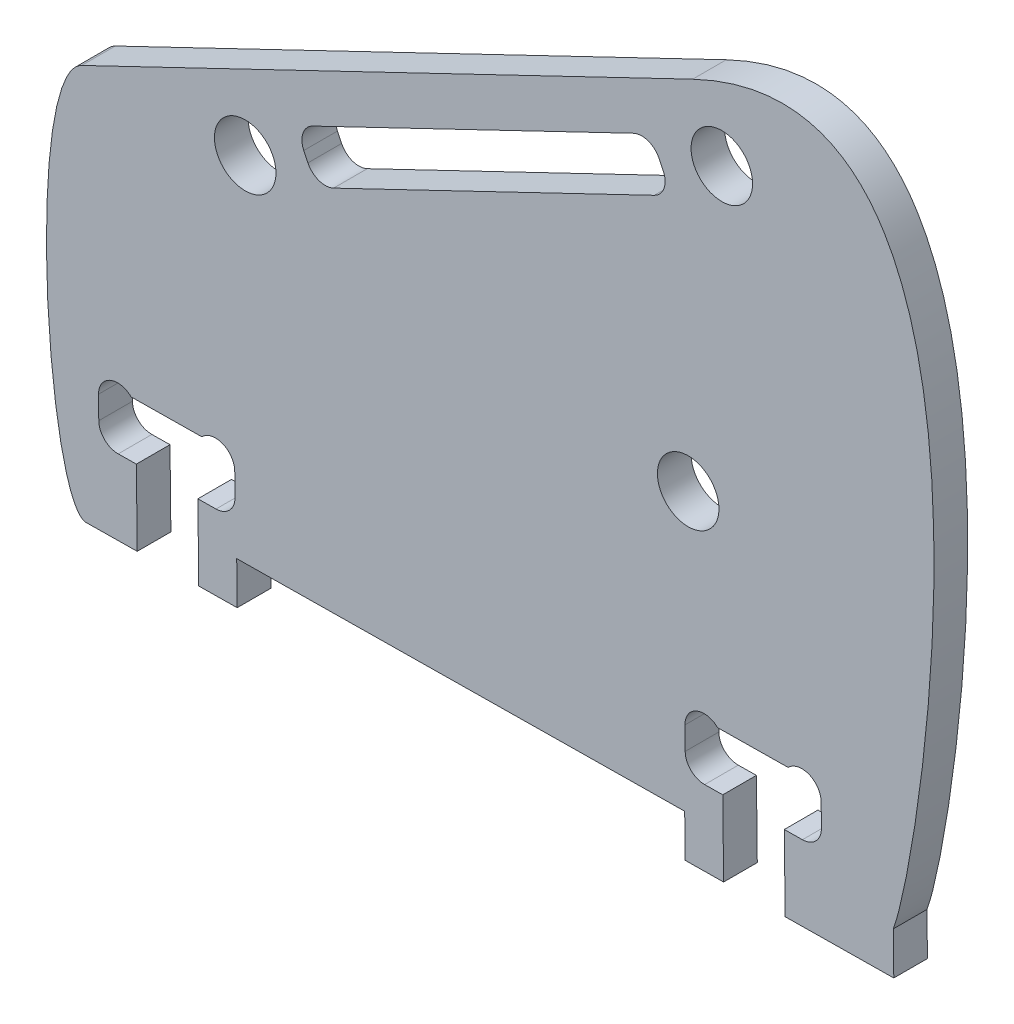
SolidWorks part; units mm, degrees
ref_plane "Front Plane" through (0, 0, 0) normal (0, 0, 1) x (1, 0, 0)
ref_plane "Top Plane" through (0, 0, 0) normal (0, 1, 0) x (1, 0, 0)
ref_plane "Right Plane" through (0, 0, 0) normal (1, 0, 0) x (0, 0, -1)
sketch "Sketch2" plane through (277.9441, -368.7823, 0) normal (0, 0, 1) x (0.9999, 0.0116, 0)
  line L0 (-273.6458, 371.9829) -> (-231.6458, 371.9829)
  line L1 (-237.0451, 403.462) -> (-231.9737, 392.5863)
  line L2 (-273.6458, 390.2567) -> (-231.6458, 390.2567) construction
  line L3 (-269.3958, 375.2829) -> (-238.8958, 375.2829) construction
  line L4 (-238.8958, 373.9829) -> (-238.8958, 371.9829) construction
  line L5 (-241.6964, 405.155) -> (-273.6458, 390.2567)
  line L6 (-273.6458, 390.2567) -> (-273.6458, 371.9829)
  line L7 (-242.1458, 376.5829) -> (-235.6458, 376.5829)
  line L8 (-265.1407, 390.3609) -> (-240.2172, 401.9829) construction
  line L9 (-260.534, 391.1298) -> (-243.7673, 398.9482)
  line L10 (-261.8629, 391.6135) -> (-262.0742, 392.0666)
  line L11 (-243.2836, 400.2771) -> (-243.4949, 400.7303)
  line L12 (-261.5905, 393.3955) -> (-244.8238, 401.214)
  line L13 (-261.4403, 390.7072) -> (-243.9175, 401.6366) construction
  line L14 (-270.1458, 388.0269) -> (-240.2172, 401.9829) construction
  line L15 (-242.861, 399.3708) -> (-262.4968, 392.9729) construction
  line L16 (-254.1458, 375.2829) -> (-254.1458, 371.9829) construction
  line L17 (-242.1458, 376.5829) -> (-242.1458, 373.9829)
  line L18 (-242.1458, 373.9829) -> (-235.6458, 373.9829)
  line L19 (-235.6458, 376.5829) -> (-235.6458, 373.9829)
  line L20 (-242.1458, 376.5829) -> (-235.6458, 373.9829) construction
  line L21 (-242.1458, 373.9829) -> (-235.6458, 376.5829) construction
  line L22 (-242.1458, 376.5829) -> (-239.5458, 373.9829) construction
  line L23 (-240.4958, 371.9829) -> (-237.2958, 371.9829)
  line L24 (-240.4958, 371.9829) -> (-240.4958, 373.9829)
  line L25 (-240.4958, 373.9829) -> (-237.2958, 373.9829)
  line L26 (-237.2958, 371.9829) -> (-237.2958, 373.9829)
  line L27 (-240.4958, 371.9829) -> (-237.2958, 373.9829) construction
  line L28 (-240.4958, 373.9829) -> (-237.2958, 371.9829) construction
  line L29 (-238.8958, 376.5829) -> (-238.8958, 373.9829) construction
  line L30 (-242.4387, 374.69) -> (-242.4387, 375.8758)
  line L31 (-235.3529, 375.8758) -> (-235.3529, 374.69)
  line L32 (-267.7958, 371.9829) -> (-267.7958, 373.9829)
  line L33 (-270.9958, 371.9829) -> (-270.9958, 373.9829)
  line L34 (-266.1458, 373.9829) -> (-272.6458, 373.9829)
  line L35 (-272.9387, 375.8758) -> (-272.9387, 374.69)
  line L36 (-266.1458, 376.5829) -> (-272.6458, 376.5829)
  line L37 (-265.8529, 374.69) -> (-265.8529, 375.8758)
  line L38 (-241.4387, 373.69) -> (-236.3529, 373.69)
  line L39 (-231.6458, 391.1072) -> (-231.6458, 371.9829)
  line L40 (-266.8529, 373.69) -> (-271.9387, 373.69)
  line L42 (-270.9958, 371.9829) -> (-273.6458, 371.9829)
  line L43 (-270.9958, 371.9829) -> (-270.9958, 369.7829)
  line L44 (-270.9958, 369.7829) -> (-273.6458, 369.7829)
  line L45 (-273.6458, 371.9829) -> (-273.6458, 369.7829)
  line L46 (-231.6458, 371.9829) -> (-237.2958, 371.9829)
  line L47 (-231.6458, 371.9829) -> (-231.6458, 369.7829)
  line L48 (-231.6458, 369.7829) -> (-237.2958, 369.7829)
  line L49 (-237.2958, 371.9829) -> (-237.2958, 369.7829)
  line L50 (-267.7958, 371.9829) -> (-265.7958, 371.9829)
  line L51 (-267.7958, 371.9829) -> (-267.7958, 369.7829)
  line L52 (-267.7958, 369.7829) -> (-265.7958, 369.7829)
  line L53 (-265.7958, 371.9829) -> (-265.7958, 369.7829)
  line L54 (-240.4958, 371.9829) -> (-242.4958, 371.9829)
  line L55 (-240.4958, 371.9829) -> (-240.4958, 369.7829)
  line L56 (-240.4958, 369.7829) -> (-242.4958, 369.7829)
  line L57 (-242.4958, 371.9829) -> (-242.4958, 369.7829)
  circle A0 centre (-242.1458, 386.4829) radius 1.6
  circle A1 centre (-265.1407, 390.3609) radius 1.6
  circle A2 centre (-240.2172, 401.9829) radius 1.6
  circle A3 centre (-270.1458, 388.0269) radius 3.5
  circle A4 centre (-240.2172, 401.9829) radius 3.5
  arc A5 (-262.0742, 392.0666) -> (-261.5905, 393.3955) centre (-261.1679, 392.4892) cw
  circle A6 centre (-235.1458, 391.1072) radius 3.5
  circle A7 centre (-241.4387, 375.8758) radius 1
  circle A8 centre (-236.3529, 375.8758) radius 1
  circle A9 centre (-236.3529, 374.69) radius 1
  circle A10 centre (-241.4387, 374.69) radius 1
  arc A11 (-261.8629, 391.6135) -> (-260.534, 391.1298) centre (-260.9566, 392.0361) ccw
  arc A12 (-243.7673, 398.9482) -> (-243.2836, 400.2771) centre (-244.1899, 399.8545) ccw
  circle A13 centre (-271.9387, 374.69) radius 1
  circle A14 centre (-271.9387, 375.8758) radius 1
  circle A15 centre (-266.8529, 375.8758) radius 1
  circle A16 centre (-266.8529, 374.69) radius 1
  arc A17 (-243.4949, 400.7303) -> (-244.8238, 401.214) centre (-244.4012, 400.3077) ccw
  spline S0 degree 3 poles (-273.6458, 369.7829) (-275.7044, 369.8278) (-276.7083, 388.8286) (-273.6458, 390.2567) knots 0 0 0 0 1 1 1 1
  spline S1 degree 3 poles (-241.6964, 405.155) (-223.9419, 413.434) (-230.011, 376.1612) (-231.6458, 371.9829) knots 0 0 0 0 1 1 1 1
  point P10 (-252.6789, 396.1719)
  point P15 (-240.2172, 401.9829)
  point P21 (-238.8958, 372.9829)
  dimension "D1" = 3.2
  dimension "D10" = 3.2
  dimension "D13" = 20.5
  dimension "D2" = 7
  dimension "D17" = 1
  dimension "D11" = 45
  dimension "D14" = 2
  dimension "D3" = 30
  dimension "D4" = 12
  dimension "D5" = 30.5
  dimension "D6" = 4.25
  dimension "D7" = 6.5
  dimension "D8" = 2.6
  dimension "D9" = 2
  dimension "D12" = 2.5
  dimension "D15" = 25
  dimension "D16" = 14.5
  dimension "D18" = 12
  dimension "D19" = 42
  dimension "D20" = 2.2
  dimension "D21" = 2
extrude "Base shape" add sketch "Sketch2" along normal blind 1.75 contours A17 L11 A4 L5 A3 L6 L0 L39 A6 L1 A12 L9 A11 L10 A5 L12 A1 A0 | A3 | A6 | A4 A2 | S0 L45 L6 | A3 L5 L6 | S1 A4 L1 A6 L39 | L0 L45 L44 L43 | L53 L0 L51 L52 | L0 L57 L56 L55 | L0 L49 L48 L47 region at (22.3547, 12.8494, 0) region at (-0.9176, 8.1883, 0) region at (1.3377, -1.0845, 0) region at (40.9915, 23.0224, 0) region at (0.2187, 18.0051, 0) region at (3.3136, 16.0836, 0) region at (6.8623, -1.0204, 0) region at (34.2042, 33.5951, 0) region at (32.1606, -0.7268, 0) region at (39.1851, -0.6453, 0) region at (38.2755, 19.5698, 0)
sketch "Sketch3" plane through (0, 0, 1.75) normal (0, 0, 1) x (1, 0, 0)
  circle A0 centre (8.2913, 18.4755) radius 3
  circle A1 centre (31.3296, 14.8646) radius 3
  circle A2 centre (33.0782, 30.3859) radius 3
  dimension "D1" = 6
extrude "Cut-Extrude2" [suppressed] cut sketch "Sketch3" against normal blind 0.3
chamfer "Chamfer1" [suppressed] distance 1.4 angle 45
sketch "Sketch4" [suppressed] plane through (0, 0, 0) normal (0, 0, -1) x (-1, 0, 0)
  circle A0 centre (-33.0782, 30.3859) radius 3
  circle A1 centre (-8.2913, 18.4755) radius 3
  circle A2 centre (-31.3296, 14.8646) radius 3
  dimension "D1" = 6
extrude "Cut-Extrude3" [suppressed] cut sketch "Sketch4" against normal blind 0.3
chamfer "Chamfer2" [suppressed] distance 1.4 angle 45
